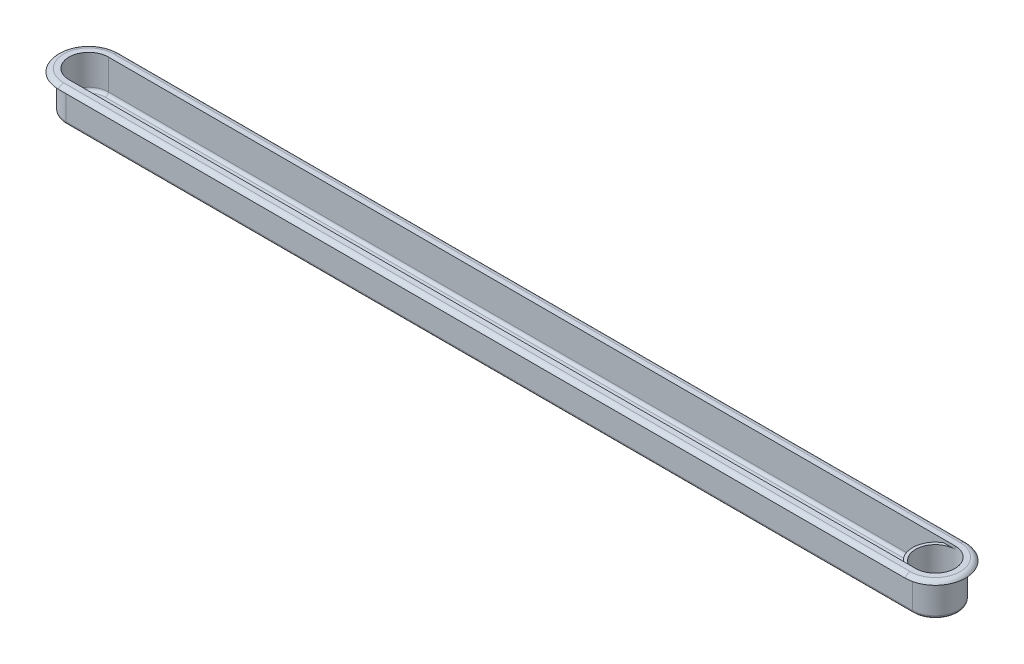
SolidWorks part; units mm, degrees
material "ABS"
ref_plane "Front Plane" through (0, 0, 0) normal (0, 0, 1) x (1, 0, 0)
ref_plane "Top Plane" through (0, 0, 0) normal (0, 1, 0) x (1, 0, 0)
ref_plane "Right Plane" through (0, 0, 0) normal (1, 0, 0) x (0, 0, -1)
sketch "Sketch1" plane through (0, 0, 0) normal (0, 1, 0) x (1, 0, 0)
  line L0 (136.3369, 0) -> (-136.3369, 0) construction
  line L1 (0, -79.7797) -> (0, 79.7797) construction
  line L2 (140, 7.5) -> (-140, 7.5)
  line L3 (-140, -7.5) -> (140, -7.5)
  arc A0 (-140, 7.5) -> (-140, -7.5) centre (-140, 0) ccw
  arc A1 (140, 7.5) -> (140, -7.5) centre (140, 0) cw
  point P4 (0, 0)
  point P8 (0, 0)
  point P18 (0, -7.5)
  point P20 (0, 7.5)
  dimension "D2" = 7.5
  dimension "D1" = 140
extrude "Boss-Extrude1" add sketch "Sketch1" along normal blind 1.5
sketch "Sketch2" plane through (0, 1.5, 0) normal (0, 1, 0) x (1, 0, 0)
  line L0 (-140, -7.5) -> (140, -7.5) construction
  line L1 (140, 7.5) -> (-140, 7.5) construction
  line L2 (-140, -7.5) -> (140, -7.5)
  line L3 (140, 7.5) -> (-140, 7.5)
  line L4 (-140, 6.5) -> (136.2583, 6.5)
  line L5 (-140, -6.5) -> (136.2583, -6.5)
  arc A0 (140, -7.5) -> (140, 7.5) centre (140, 0) ccw construction
  arc A1 (-140, 7.5) -> (-140, -7.5) centre (-140, 0) ccw construction
  arc A2 (140, -7.5) -> (140, 7.5) centre (140, 0) ccw
  arc A3 (-140, 7.5) -> (-140, -7.5) centre (-140, 0) ccw
  circle A4 centre (140, 0) radius 6.5
  arc A5 (-140, 6.5) -> (-140, -6.5) centre (-140, 0) ccw
  arc A6 (136.2583, 6.5) -> (136.2583, -6.5) centre (140, 0) ccw
  dimension "D1" = 13
  dimension "D2" = 7.5
extrude "Boss-Extrude2" add sketch "Sketch2" along normal blind 10
sketch "Sketch3" plane through (0, 11.5, 0) normal (0, 1, 0) x (1, 0, 0)
  line L0 (-140, -6.5) -> (136.2583, -6.5) construction
  line L1 (136.2583, 6.5) -> (-140, 6.5) construction
  line L2 (-140, -6.5) -> (136.2583, -6.5)
  line L3 (136.2583, 6.5) -> (-140, 6.5)
  line L4 (140, 6.5) -> (136.2583, 6.5)
  line L5 (140, -6.5) -> (136.2583, -6.5)
  line L6 (-140, 10) -> (140, 10)
  line L7 (140, -10) -> (-140, -10)
  arc A0 (-140, 6.5) -> (-140, -6.5) centre (-140, 0) ccw construction
  arc A1 (-140, 6.5) -> (-140, -6.5) centre (-140, 0) ccw
  arc A3 (140, -6.5) -> (140, 6.5) centre (140, 0) ccw
  circle A4 centre (140, 0) radius 6.5 construction
  arc A5 (-140, 10) -> (-140, -10) centre (-140, 0) ccw
  arc A6 (140, 10) -> (140, -10) centre (140, 0) cw
  dimension "D1" = 3.5
extrude "Boss-Extrude3" add sketch "Sketch3" along normal blind 1
fillet "Fillet1" radius 2 4 edges at (-150, 12.5, 0) (0, 12.5, 10) (150, 12.5, 0) (0, 12.5, -10)
fillet "Fillet2" radius 1 4 edges at (-147.5, 0, 0) (0, 0, 7.5) (147.5, 0, 0) (0, 0, -7.5)
fillet "Fillet3" radius 1 3 edges at (-1.8708, 1.5, 6.5) (-146.5, 1.5, 0) (-1.8708, 1.5, -6.5)
sketch "Sketch4" plane through (0, 1.5, 0) normal (0, 1, 0) x (1, 0, 0)
  line L0 (159.0961, 0) -> (-159.0961, 0) construction
  line L1 (-123.5, 3.5) -> (-103.5, 3.5)
  line L2 (-103.5, -3.5) -> (-123.5, -3.5)
  arc A0 (-103.5, 3.5) -> (-103.5, -3.5) centre (-103.5, 0) cw
  arc A1 (-123.5, -3.5) -> (-123.5, 3.5) centre (-123.5, 0) cw
  point P4 (0, 0)
  point P14 (-100, 0)
  dimension "D2" = 3.5
  dimension "D3" = 100
  dimension "D1" = 20
extrude "Cut-Extrude1" cut sketch "Sketch4" against normal through all
sketch "Sketch5" plane through (0, 1.5, 0) normal (0, 1, 0) x (1, 0, 0)
  circle A0 centre (140, 0) radius 0.75
  dimension "D1" = 1.5
extrude "Cut-Extrude2" cut sketch "Sketch5" against normal through all
